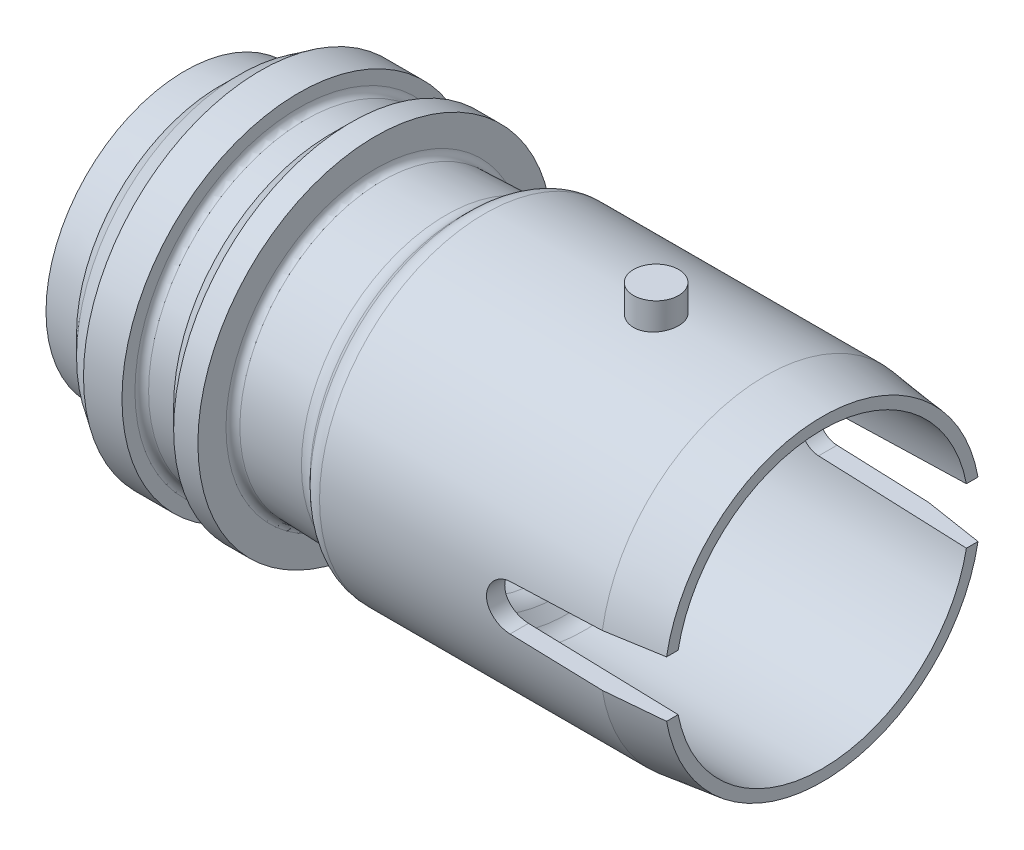
SolidWorks part; units mm, degrees
ref_plane "Front Plane" through (0, 0, 0) normal (0, 0, 1) x (1, 0, 0)
ref_plane "Top Plane" through (0, 0, 0) normal (0, 1, 0) x (1, 0, 0)
ref_plane "Right Plane" through (0, 0, 0) normal (1, 0, 0) x (0, 0, -1)
sketch "Sketch1" plane through (0, 0, 0) normal (0, 0, 1) x (1, 0, 0)
  line L0 (-11.7761, 0) -> (32.5958, 0) construction
  line L1 (-40.64, 13.7795) -> (0, 13.7795)
  line L2 (0, 13.7795) -> (0, 16.383)
  line L3 (0, 16.383) -> (30.48, 16.383)
  line L8 (-40.64, 14.732) -> (-40.64, 13.7795)
  line L9 (-7.62, 18.415) -> (24.13, 18.415)
  line L10 (24.13, 18.415) -> (30.48, 17.653)
  line L11 (30.48, 17.653) -> (30.48, 16.383)
  line L12 (-40.64, 14.732) -> (-33.782, 15.621) construction
  line L13 (-33.782, 15.621) -> (-33.782, 17.78) construction
  line L14 (-33.782, 17.78) -> (-32.004, 18.9611) construction
  line L15 (-32.004, 18.9611) -> (-28.702, 18.9611) construction
  line L16 (-28.702, 18.9611) -> (-28.702, 16.7513) construction
  line L17 (-28.702, 16.7513) -> (-21.336, 16.7513) construction
  line L18 (-21.336, 16.7513) -> (-21.336, 19.0373) construction
  line L19 (-21.336, 19.0373) -> (-19.3929, 19.0373) construction
  line L20 (-19.3929, 19.0373) -> (-19.3929, 15.875)
  line L21 (-19.3929, 15.875) -> (-7.62, 16.256)
  line L22 (-7.62, 18.415) -> (-7.62, 16.256)
  line L23 (-22.098, 19.7993) -> (-19.3929, 19.7993)
  line L34 (-40.64, 15.5004) -> (-34.544, 16.2906) construction
  line L35 (-34.544, 16.2906) -> (-34.544, 18.1886) construction
  line L36 (-34.544, 18.1886) -> (-32.234, 19.7231)
  line L37 (-32.234, 19.7231) -> (-27.94, 19.7231)
  line L38 (-27.94, 19.7231) -> (-27.94, 17.5133)
  line L39 (-27.94, 17.5133) -> (-22.098, 17.5133) construction
  line L40 (-22.098, 17.5133) -> (-22.098, 19.7993) construction
  line L41 (-19.3929, 19.0373) -> (-19.3929, 19.7993)
  line L42 (-22.098, 19.7993) -> (-18.6309, 19.7993) construction
  line L43 (-18.6309, 19.7993) -> (-18.6309, 16.6621) construction
  line L44 (-18.6309, 16.6621) -> (-8.382, 16.9937) construction
  line L45 (-8.382, 19.177) -> (-8.382, 16.9937) construction
  line L46 (-8.382, 19.177) -> (24.1756, 19.177) construction
  line L47 (24.1756, 19.177) -> (31.242, 18.329) construction
  line L48 (31.242, 18.329) -> (31.242, 15.621) construction
  line L49 (0.762, 15.621) -> (31.242, 15.621) construction
  line L50 (0.762, 13.0175) -> (0.762, 15.621) construction
  line L51 (-41.402, 13.0175) -> (0.762, 13.0175) construction
  line L52 (-41.402, 15.4016) -> (-41.402, 13.0175) construction
  line L53 (-40.64, 14.732) -> (-40.64, 15.5004)
  line L54 (-41.402, 15.4016) -> (-34.544, 16.2906) construction
  line L55 (-22.098, 19.7993) -> (-24.384, 17.5133)
  line L56 (-34.544, 18.1886) -> (-36.7247, 16.0079)
  line L57 (-24.384, 17.5133) -> (-27.94, 17.5133)
  line L58 (-36.7247, 16.0079) -> (-40.64, 15.5004)
  dimension "D1" = 36.83
  dimension "D2" = 32.766
  dimension "D3" = 35.306
  dimension "D4" = 38.1
  dimension "D5" = 27.559
  dimension "D6" = 29.464
  dimension "D7" = 6.858
  dimension "D8" = 6.35
  dimension "D9" = 30.48
  dimension "D10" = 7.366
  dimension "D11" = 1.9431
  dimension "D12" = 31.242
  dimension "D13" = 18.9611
  dimension "D14" = 5.08
  dimension "D15" = 16.7513
  dimension "D16" = 31.75
  dimension "D17" = 32.512
  dimension "D18" = 35.56
  dimension "D19" = 3.302
  dimension "D20" = 33.02
  dimension "D21" = 19.0373
  dimension "D23" = 45
  dimension "D24" = 45
  dimension "D22" = 0.762
revolve "Revolve1" add sketch "Sketch1" angle 360 about L0
sketch "Sketch2" plane through (0, 0, 0) normal (0, 0, 1) x (1, 0, 0)
  line L0 (13.8824, 2.5385) -> (30.48, 3.1115)
  line L1 (30.48, 3.1115) -> (30.48, -3.1115)
  line L2 (30.48, -3.1115) -> (13.8824, -2.5385)
  line L4 (55, 0) -> (-55, 0) construction
  line L5 (30.48, -17.653) -> (30.48, 17.653) construction
  arc A0 (13.8824, 2.5385) -> (13.8824, -2.5385) centre (13.97, 0) ccw
  dimension "D1" = 2.54
  dimension "D3" = 16.51
  dimension "D2" = 6.223
extrude "Cut-Extrude3" cut sketch "Sketch2" against normal through all both and the other way through all
ref_plane "Plane1" through (0, 21.336, 0) normal (0, 1, 0) x (1, 0, 0)
sketch "Sketch3" plane through (0, 21.336, 0) normal (0, 1, 0) x (1, 0, 0)
  line L0 (30.48, -17.3766) -> (30.48, 17.3766) construction
  circle A0 centre (11.938, 0) radius 2.5146
  dimension "D1" = 5.0292
  dimension "D2" = 18.542
extrude "Boss-Extrude1" add sketch "Sketch3" against normal up to surface (3.0935 mm away) up to face at (-7.62, 0, 18.415)
mirror "Mirror1" about plane through (0, 0, 0) normal (0, 1, 0) of "Boss-Extrude1"
fillet "Fillet1" radius 0.762 2 edges at (-19.3929, 0, 15.875) (-27.94, 0, 17.5133)
chamfer "Chamfer1" distance 2.794 angle 45 2 edges at (0, 0, 16.383) (-7.62, 0, 16.256) first distance on face at (0, 0, 16.383) first distance on face at (-7.62, 0, 16.256)
fillet "Fillet3" radius 2.54 4 edges at (2.794, 0, 16.383) (-8.255, 0, -18.415) (-10.5074, 0, -16.1626) (0.1905, 0, -13.7795)
